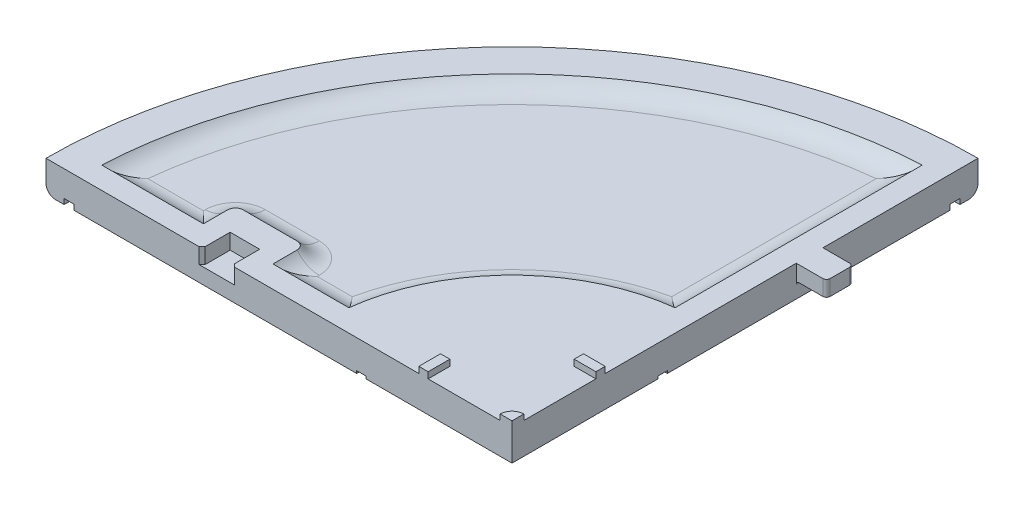
SolidWorks part; units mm, degrees
ref_plane "Front Plane" through (0, 0, 0) normal (0, 0, 1) x (1, 0, 0)
ref_plane "Top Plane" through (0, 0, 0) normal (0, 1, 0) x (1, 0, 0)
ref_plane "Right Plane" through (0, 0, 0) normal (1, 0, 0) x (0, 0, -1)
sketch "Sketch1" plane through (0, 0, 0) normal (0, 1, 0) x (1, 0, 0)
  circle A0 centre (0, 0) radius 150
extrude "Boss-Extrude3" add sketch "Sketch1" along normal blind 10
sketch "Sketch4" plane through (0, 10, 0) normal (0, 1, 0) x (1, 0, 0)
  line L0 (0, 0) -> (0, 162.3297)
  line L1 (0, 162.3297) -> (183.6782, 162.3297)
  line L2 (183.6782, 162.3297) -> (183.6782, -176.4278)
  line L3 (183.6782, -176.4278) -> (-217.9165, -176.4278)
  line L4 (-217.9165, -176.4278) -> (-217.9165, 0)
  line L5 (-217.9165, 0) -> (0, 0)
extrude "Cut-Extrude2" cut sketch "Sketch4" against normal blind 10
sketch "Sketch5" plane through (0, 10, 0) normal (0, 1, 0) x (1, 0, 0)
  line L0 (0, 3.825) -> (0, 0)
  line L1 (0, 0) -> (-3.825, 0)
  arc A0 (0, 3.825) -> (-3.825, 0) centre (0, 0) ccw
extrude "Boss-Extrude4" add sketch "Sketch5" along normal blind 1.8
sketch "Sketch6" plane through (0, 10, 0) normal (0, 1, 0) x (1, 0, 0)
  line L1 (-3.825, 0) -> (-150, 0) construction
  line L2 (-27, 0) -> (-27, 7)
  line L3 (-27, 7) -> (-30, 7)
  line L4 (-30, 7) -> (-30, 0)
  line L5 (-27, 0) -> (-30, 0)
extrude "Boss-Extrude5" add sketch "Sketch6" along normal blind 2
sketch "Sketch7" plane through (0, 10, 0) normal (0, 1, 0) x (1, 0, 0)
  line L1 (0, 150) -> (0, 3.825) construction
  line L2 (0, 27) -> (-7, 27)
  line L3 (-7, 27) -> (-7, 30)
  line L4 (-7, 30) -> (0, 30)
  line L5 (0, 30) -> (0, 27)
extrude "Boss-Extrude6" add sketch "Sketch7" along normal blind 2
sketch "Sketch8" plane through (0, 10, 0) normal (0, 1, 0) x (1, 0, 0)
  line L0 (0, 0) -> (-90, 0)
  line L1 (-30, 0) -> (-150, 0) construction
  line L2 (-90, 0) -> (-90, 10)
  line L3 (-90, 10) -> (-100, 10)
  line L4 (-100, 10) -> (-100, 0)
  line L5 (-100, 0) -> (-90, 0)
  line M8 (-150, 0) -> (-30, 0)
extrude "Cut-Extrude3" cut sketch "Sketch8" against normal blind 5 contours L3 L4 L2 M8 region at (-95, 10, -5)
sketch "Sketch9" plane through (0, 10, 0) normal (0, 1, 0) x (1, 0, 0)
  line L0 (0, 0) -> (0, 91)
  line L1 (0, 150) -> (0, 30) construction
  line L2 (0, 91) -> (9.1938, 91)
  line L3 (9.1938, 91) -> (9.1938, 99.2773)
  line L4 (9.1938, 99.2773) -> (0, 99.2773)
  line L5 (0, 99.2773) -> (0, 91)
  line M13 (0, 30) -> (0, 150)
extrude "Boss-Extrude7" add sketch "Sketch9" against normal blind 4.35 contours L3 L4 L2 M13 region at (4.5969, 10, -95.1387)
chamfer "Chamfer1" distance 1 angle 45 2 edges at (9.1938, 7.825, -91) (9.1938, 7.825, -99.2773)
sketch "Sketch10" plane through (0, 0, 0) normal (0, -1, 0) x (1, 0, 0)
  line L0 (-140.9265, 0) -> (-144.1784, 0)
  line L1 (0, -140.9265) -> (0, -144.1784)
  arc A0 (-144.1784, 0) -> (0, -144.1784) centre (0, 0) ccw
  arc A1 (-140.9265, 0) -> (0, -140.9265) centre (0, 0) ccw
extrude "Cut-Extrude4" cut sketch "Sketch10" against normal blind 1.7
sketch "Sketch11" plane through (0, 0, 0) normal (0, -1, 0) x (-1, 0, 0)
  line L0 (47, 0) -> (50, 0)
  line L1 (47, 0) -> (50, 0)
  line L2 (0, 47) -> (0, 50)
  line L3 (0, 50) -> (50, 50)
  line L4 (50, 0) -> (50, 50)
  line L7 (0, 47) -> (47, 47)
  line L8 (47, 0) -> (47, 47)
  line L9 (0, 47) -> (0, 50)
extrude "Cut-Extrude5" cut sketch "Sketch11" against normal blind 0.8 contours L8 L3 L4 L7 region at (-47.7071, 0, -23.5)
fillet "Fillet1" radius 3 1 edges at (-106.066, 0, -106.066)
fillet "Fillet2" radius 1.4 1 edges at (0, 5.65, -95.1387)
sketch "Sketch12" plane through (0, 0, 0) normal (0, -1, 0) x (-1, 0, 0)
  line L0 (0, 140.9265) -> (0, 50) construction
  line L1 (0, 90.4203) -> (-10.6719, 90.4203)
  line L2 (0, 90.4203) -> (0, 100.1105)
  line L3 (0, 100.1105) -> (-10.6719, 100.1105)
  line L4 (-10.6719, 90.4203) -> (-10.6719, 100.1105)
extrude "Cut-Extrude6" cut sketch "Sketch12" against normal blind 11
sketch "Sketch13" plane through (0, 0, 0) normal (0, -1, 0) x (-1, 0, 0)
  line L0 (0, 0) -> (0, 91.5)
  line L1 (0, 140.9265) -> (0, 50) construction
  line L2 (0, 91.5) -> (-9.7311, 91.5)
  line L3 (-9.7311, 91.5) -> (-9.7311, 100.1)
  line L4 (-9.7311, 100.1) -> (0, 100.1)
  line L5 (0, 100.1) -> (0, 91.5)
extrude "Boss-Extrude8" add sketch "Sketch13" against normal blind 10 contours L5 L4 L3 L2 region at (4.8656, 0, -95.8)
sketch "Sketch14" plane through (0, 0, 0) normal (0, -1, 0) x (-1, 0, 0)
  line L0 (0, 91.5) -> (0, 100.1)
  line L1 (0, 100.1) -> (-9.7311, 100.1)
  line L2 (-9.7311, 100.1) -> (-9.7311, 91.5)
  line L3 (-9.7311, 91.5) -> (0, 91.5)
extrude "Cut-Extrude7" cut sketch "Sketch14" against normal blind 5
fillet "Fillet3" radius 1 1 edges at (0, 5, -95.8)
fillet "Fillet4" radius 1.2 2 edges at (9.7311, 7.5, -100.1) (9.7311, 7.5, -91.5)
sketch "Sketch15" plane through (0, 10, 0) normal (0, 1, 0) x (1, 0, 0)
  line L0 (-84.0102, 7.0711) -> (-84.0102, 17.3414)
  line L1 (-59.5819, 7.0711) -> (-84.0102, 7.0711)
  line L2 (-7.0711, 59.5819) -> (-7.0711, 139.1414)
  line L3 (-84.0102, 17.3414) -> (-106.3858, 17.3414)
  line L4 (-106.3858, 17.3414) -> (-106.3858, 7.0711)
  line L5 (-106.3858, 7.0711) -> (-139.1414, 7.0711)
  arc A0 (-7.0711, 59.5819) -> (-59.5819, 7.0711) centre (0, 0) ccw
  arc A1 (-7.0711, 139.1414) -> (-139.1414, 7.0711) centre (0, 0) ccw
extrude "Cut-Extrude8" cut sketch "Sketch15" against normal blind 3.5
fillet "Fillet5" radius 2.5 2 edges at (-84.0102, 8.25, -17.3414) (-106.3858, 8.25, -17.3414)
fillet "Fillet6" radius 9 8 edges at (-105.6535, 6.5, -16.6091) (-84.7425, 6.5, -16.6091) (-98.5148, 6.5, -98.5148) (-122.7636, 6.5, -7.0711) (-95.198, 6.5, -17.3414) (-71.7961, 6.5, -7.0711) (-7.0711, 6.5, -99.3616) (-42.4264, 6.5, -42.4264)
sketch "Sketch16" plane through (0, 0, 0) normal (0, 0, 1) x (1, 0, 0)
  line L0 (-90, 10) -> (-100, 10) construction
  line L1 (-100, 5) -> (-99.75, 5)
  line L2 (-100, 5) -> (-100, 10)
  line L3 (-100, 10) -> (-99.75, 10)
  line L4 (-99.75, 5) -> (-99.75, 10)
  line L6 (-90, 5) -> (-90.25, 5)
  line L7 (-90, 5) -> (-90, 10)
  line L8 (-90, 10) -> (-90.25, 10)
  line L9 (-90.25, 5) -> (-90.25, 10)
extrude "Boss-Extrude9" add sketch "Sketch16" against normal blind 11.5
sketch "Sketch17" plane through (0, 0, -10) normal (0, 0, 1) x (1, 0, 0)
  line L1 (-99.75, 10) -> (-90.25, 10)
  line L2 (-99.75, 10) -> (-99.75, 5)
  line L3 (-99.75, 5) -> (-90.25, 5)
  line L4 (-90.25, 10) -> (-90.25, 5)
extrude "Boss-Extrude12" add sketch "Sketch17" along normal blind 0.13
sketch "Sketch19" plane through (0, 0, -9.87) normal (0, 0, 1) x (1, 0, 0)
  line L1 (-99.75, 10) -> (-90.25, 10)
  line L2 (-99.75, 10) -> (-99.75, 5)
  line L3 (-99.75, 5) -> (-90.25, 5)
  line L4 (-90.25, 10) -> (-90.25, 5)
extrude "Boss-Extrude13" add sketch "Sketch19" along normal blind 0.85
chamfer "Chamfer2" distance 1 angle 45 2 edges at (-90.25, 7.5, 0) (-99.75, 7.5, 0)
